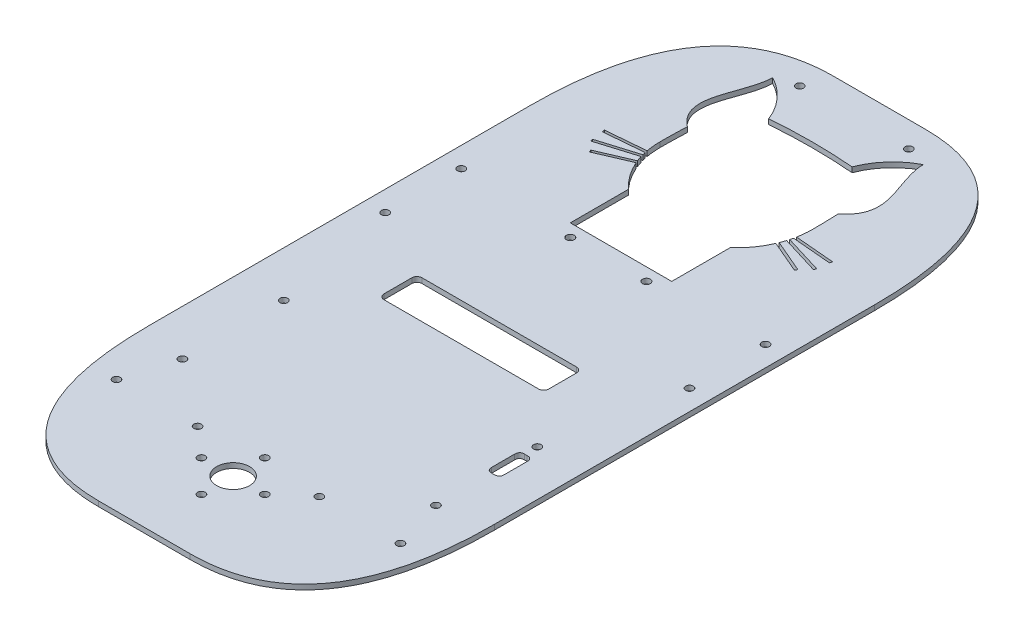
SolidWorks part; units mm, degrees
ref_plane "Спереди" through (0, 0, 0) normal (0, 0, 1) x (1, 0, 0)
ref_plane "Сверху" through (0, 0, 0) normal (0, 1, 0) x (1, 0, 0)
ref_plane "Справа" through (0, 0, 0) normal (1, 0, 0) x (0, 0, -1)
sketch "Эскиз1" plane through (0, 0, 0) normal (0, 1, 0) x (1, 0, 0)
  line L0 (0, 160) -> (0, -130) construction
  line L1 (-68, 160) -> (68, 160)
  line L2 (-68, 160) -> (-68, -130)
  line L3 (-68, -130) -> (68, -130)
  line L4 (68, 160) -> (68, -130)
  line L5 (-68, 0) -> (68, 0) construction
  dimension "D1" = 136
  dimension "D2" = 160
  dimension "D3" = 130
extrude "тело" add sketch "Эскиз1" along normal blind 2
sketch "Эскиз12" plane through (0, 2, 0) normal (0, 1, 0) x (1, 0, 0)
  line L0 (0, 160) -> (0, -130) construction
  line L1 (68, 160) -> (-68, 160) construction
  line L2 (-68, -130) -> (68, -130) construction
  line L3 (60, 55) -> (60, 25) construction
  line L4 (60, 40) -> (-60, 40) construction
  line L5 (-60, 55) -> (-60, 25) construction
  circle A0 centre (60, 55) radius 1.5
  circle A1 centre (-60, 55) radius 1.5
  circle A2 centre (-60, 25) radius 1.5
  circle A3 centre (60, 25) radius 1.5
  point P12 (-60, 40)
  point P17 (0, 40)
  dimension "D2" = 3
  dimension "D1" = 30
  dimension "D3" = 60
  dimension "D4" = 40
extrude "крепление подвески" cut sketch "Эскиз12" against normal through all
sketch "Эскиз8" plane through (0, 2, 0) normal (0, 1, 0) x (1, 0, 0)
  line L0 (-20, -130) -> (20, -130) construction
  line L1 (0, -130) -> (0, 160) construction
  line L2 (-68, -130) -> (68, -130) construction
  line L3 (68, 160) -> (-68, 160) construction
  circle A0 centre (-20, -130) radius 1.5
  circle A1 centre (20, -130) radius 1.5
  point P10 (0, -130)
  dimension "D1" = 3
  dimension "D2" = 40
  dimension "D3" = 130
extrude "крепление камеры" [suppressed] cut sketch "Эскиз8" against normal through all and the other way through all
sketch "Эскиз13" plane through (0, 2, 0) normal (0, 1, 0) x (1, 0, 0)
  line L0 (0, 160) -> (0, -130) construction
  line L1 (68, 160) -> (-68, 160) construction
  line L2 (-68, -130) -> (68, -130) construction
  line L3 (-57, 125) -> (57, 125) construction
  line L4 (-68, 15) -> (68, 15) construction
  line L5 (-57, -10) -> (57, -10) construction
  line L6 (-68, 160) -> (-68, -130) construction
  line L7 (-57, -85) -> (57, -85) construction
  line L8 (68, -130) -> (68, 160) construction
  line L9 (-25, 125) -> (-57, 125) construction
  line L10 (25, 125) -> (57, 125) construction
  line L11 (-57, -10) -> (-25, -10) construction
  line L12 (25, -10) -> (57, -10) construction
  line L13 (-57, -85) -> (-25, -85) construction
  line L14 (25, -85) -> (57, -85) construction
  circle A0 centre (-57, 125) radius 1.5
  circle A1 centre (57, 125) radius 1.5
  circle A2 centre (57, -10) radius 1.5
  circle A3 centre (-57, -10) radius 1.5
  circle A4 centre (-57, -85) radius 1.5
  circle A5 centre (57, -85) radius 1.5
  circle A6 centre (-25, 125) radius 1.5
  circle A7 centre (25, 125) radius 1.5
  circle A8 centre (25, -10) radius 1.5
  circle A9 centre (-25, -10) radius 1.5
  circle A10 centre (-25, -85) radius 1.5
  circle A11 centre (25, -85) radius 1.5
  point P18 (0, 125)
  point P19 (0, -10)
  point P20 (0, -85)
  point P27 (0, 15)
  dimension "D1" = 3
  dimension "D2" = 110
  dimension "D3" = 25
  dimension "D4" = 100
  dimension "D5" = 114
  dimension "D6" = 32
  dimension "D7" = 32
  dimension "D8" = 32
  dimension "D9" = 32
  dimension "D10" = 32
  dimension "D11" = 32
extrude "крепления уголков" [suppressed] cut sketch "Эскиз13" against normal through all
sketch "Эскиз9" plane through (0, 2, 0) normal (0, 1, 0) x (1, 0, 0)
  line L1 (-68, -130) -> (68, -130) construction
  circle A0 centre (0, -95) radius 6.5
  circle A1 centre (0, -95) radius 12.5 construction
  circle A2 centre (0, -82.5) radius 1.5
  circle A3 centre (12.5, -95) radius 1.5
  circle A4 centre (-12.5, -95) radius 1.5
  circle A5 centre (0, -107.5) radius 1.5
  dimension "D2" = 13
  dimension "D3" = 25
  dimension "D4" = 3
  dimension "D1" = 35
extrude "ось вращения качалки" cut sketch "Эскиз9" against normal through all
sketch "Эскиз5" plane through (0, 2, 0) normal (0, 1, 0) x (1, 0, 0)
  line L0 (-50, -65) -> (50, -25) construction
  line L1 (-50, -25) -> (50, -25) construction
  line L2 (-50, -25) -> (-50, -65) construction
  line L3 (-50, -65) -> (50, -65) construction
  line L4 (50, -25) -> (50, -65) construction
  line L5 (-50, -25) -> (50, -65) construction
  line L6 (-68, -130) -> (68, -130) construction
  circle A0 centre (-50, -25) radius 1.5
  circle A1 centre (50, -25) radius 1.5
  circle A2 centre (50, -65) radius 1.5
  circle A3 centre (-50, -65) radius 1.5
  point P12 (0, -45)
  dimension "D1" = 3
  dimension "D2" = 100
  dimension "D3" = 40
  dimension "D4" = 65
extrude "крепление raspberry" cut sketch "Эскиз5" against normal through all
sketch "Эскиз11" plane through (0, 2, 0) normal (0, 1, 0) x (1, 0, 0)
  line L0 (-32.5, 2.5) -> (32.5, 2.5) construction
  line L1 (-32.5, 10) -> (32.5, 10)
  line L2 (-32.5, 10) -> (-32.5, -5)
  line L3 (-32.5, -5) -> (32.5, -5)
  line L4 (32.5, 10) -> (32.5, -5)
  circle A0 centre (50, -25) radius 1.5 construction
  point P11 (0, 10)
  dimension "D3" = 20
  dimension "D1" = 65
  dimension "D2" = 15
extrude "отверстие под провода на нижний этаж" cut sketch "Эскиз11" against normal through all
fillet "Скругление3" radius 2 4 edges at (-32.5, 1, 5) (32.5, 1, 5) (32.5, 1, -10) (-32.5, 1, -10)
sketch "Эскиз14" plane through (0, 2, 0) normal (0, 1, 0) x (1, 0, 0)
  line L0 (0, 160) -> (0, -130) construction
  line L1 (68, 160) -> (-68, 160) construction
  line L2 (-68, -130) -> (68, -130) construction
  line L3 (-47.5, -125) -> (47.5, -125) construction
  line L4 (47.5, -115) -> (47.5, -135) construction
  line L5 (-12.5, -95) -> (12.5, -95) construction
  line L6 (-47.5, -115) -> (-47.5, -135) construction
  circle A0 centre (-47.5, -115) radius 1.5
  circle A1 centre (-47.5, -135) radius 1.5
  circle A2 centre (47.5, -115) radius 1.5
  circle A3 centre (47.5, -135) radius 1.5
  point P8 (0, -125)
  point P14 (-47.5, -125)
  point P15 (47.5, -125)
  dimension "D1" = 3
  dimension "D2" = 20
  dimension "D3" = 30
  dimension "D4" = 95
extrude "крепление стопоров" [suppressed] cut sketch "Эскиз14" against normal through all
sketch "Эскиз15" plane through (0, 2, 0) normal (0, 1, 0) x (1, 0, 0)
  line L0 (-21.5, 150) -> (21.5, 150) construction
  line L1 (68, 160) -> (-68, 160) construction
  circle A0 centre (21.5, 150) radius 1.5
  circle A1 centre (-21.5, 150) radius 1.5
  point P6 (0, 150)
  dimension "D1" = 3
  dimension "D2" = 10
  dimension "D3" = 43
extrude "Крепление фронтальной камеры" cut sketch "Эскиз15" against normal up to next
sketch "Эскиз16" plane through (0, 2, 0) normal (0, 1, 0) x (1, 0, 0)
  line L0 (-56, -85) -> (-24, -85) construction
  line L1 (-68, -130) -> (68, -130) construction
  line L2 (-68, 160) -> (-68, -130) construction
  line L3 (0, -130) -> (0, 160) construction
  line L4 (68, 160) -> (-68, 160) construction
  circle A0 centre (-56, -85) radius 1.5
  circle A1 centre (-24, -85) radius 1.5
  circle A2 centre (24, -85) radius 1.5
  circle A3 centre (56, -85) radius 1.5
  dimension "D1" = 32
  dimension "D4" = 3
  dimension "D2" = 45
  dimension "D3" = 12
extrude "Крепление силовых уголков со стороны буллета" cut sketch "Эскиз16" against normal up to next
sketch "Эскиз17" plane through (0, 2, 0) normal (0, 1, 0) x (1, 0, 0)
  line L1 (48, -30) -> (53, -30)
  line L2 (48, -30) -> (48, -43)
  line L3 (48, -43) -> (53, -43)
  line L4 (53, -30) -> (53, -43)
  circle A0 centre (50, -25) radius 1.5 construction
  dimension "D4" = 3
  dimension "D1" = 5
  dimension "D2" = 13
  dimension "D3" = 5
extrude "Отверстие по дпитание сервоприводов и шилда" cut sketch "Эскиз17" against normal up to next
sketch "Эскиз18" plane through (0, 2, 0) normal (0, 1, 0) x (1, 0, 0)
  line L0 (0, 0) -> (0, 160) construction
  line L1 (68, 160) -> (-68, 160) construction
  line L2 (-20, 58) -> (20, 58)
  line L3 (20, 58) -> (20, 81)
  line L5 (-20, 81) -> (-20, 58)
  line L6 (10, 58) -> (10, 43)
  line L7 (10, 43) -> (-10, 43)
  line L8 (-10, 43) -> (-10, 58)
  line L9 (28.2843, 93.3607) -> (-28.2843, 93.3607)
  line L11 (-29.2696, 96.7813) -> (-44.8695, 95.4286)
  line L12 (15, 53) -> (-15, 53) construction
  line L13 (-28.6963, 94.613) -> (-43.9353, 89.9676)
  line L16 (-27.5654, 91.5223) -> (-40.4203, 86.0016)
  line L17 (-29.474, 97.7673) -> (-44.9559, 96.4249)
  line L18 (-28.972, 95.5744) -> (-44.2269, 90.9242)
  line L19 (-27.9447, 92.4477) -> (-40.8149, 86.9204)
  line L20 (-44.9559, 96.4249) -> (-44.8695, 95.4286)
  line L21 (-44.2269, 90.9242) -> (-43.9353, 89.9676)
  line L22 (-40.8149, 86.9204) -> (-40.4203, 86.0016)
  line L23 (-29.356, 97.7776) -> (-44.9559, 96.4249) construction
  line L24 (-28.6804, 94.6179) -> (-43.9353, 89.9676) construction
  line L25 (-27.5501, 91.5289) -> (-40.4203, 86.0016) construction
  line L26 (40.8149, 86.9204) -> (40.4203, 86.0016)
  line L27 (44.2269, 90.9242) -> (43.9353, 89.9676)
  line L28 (44.9559, 96.4249) -> (44.8695, 95.4286)
  line L29 (27.9447, 92.4477) -> (40.8149, 86.9204)
  line L30 (28.972, 95.5744) -> (44.2269, 90.9242)
  line L31 (29.474, 97.7673) -> (44.9559, 96.4249)
  line L32 (27.5654, 91.5223) -> (40.4203, 86.0016)
  line L33 (28.6963, 94.613) -> (43.9353, 89.9676)
  line L34 (29.2696, 96.7813) -> (44.8695, 95.4286)
  arc A0 (20, 81) -> (-20, 81) centre (0, 103.3607) ccw construction
  circle A1 centre (15, 53) radius 1.55
  circle A2 centre (-15, 53) radius 1.55
  circle A3 centre (-50, -25) radius 1.5 construction
  arc A4 (-30, 103.3607) -> (-28.2843, 131.3607) centre (199.3322, 103.3607) cw
  arc A5 (-28.2843, 131.3607) -> (28.2843, 131.3607) centre (0, -67.6393) cw
  arc A6 (28.2843, 131.3607) -> (30, 103.3607) centre (-199.3322, 103.3607) cw
  arc A7 (-20, 81) -> (-27.5654, 91.5223) centre (0, 103.3607) cw
  arc A8 (20, 81) -> (27.5654, 91.5223) centre (0, 103.3607) ccw
  arc A9 (29.474, 97.7673) -> (30, 103.3607) centre (0, 103.3607) ccw
  arc A10 (-29.7135, 147.5209) -> (-16.4423, 132.687) centre (-42.569, 122.6661) cw
  arc A11 (29.7135, 147.5209) -> (16.4423, 132.687) centre (42.569, 122.6661) ccw
  arc A12 (28.972, 95.5744) -> (29.2696, 96.7813) centre (0, 103.3607) ccw
  arc A13 (27.9447, 92.4477) -> (28.6963, 94.613) centre (0, 103.3607) ccw
  arc A14 (-27.9447, 92.4477) -> (-28.6963, 94.613) centre (0, 103.3607) cw
  arc A15 (-28.972, 95.5744) -> (-29.2696, 96.7813) centre (0, 103.3607) cw
  arc A16 (-29.474, 97.7673) -> (-30, 103.3607) centre (0, 103.3607) cw
  spline S0 degree 3 poles (-29.7571, 113.9123) (-42.1018, 123.5014) (-29.7562, 136.265) (-29.7135, 147.5209) knots 0 0 0 0 1 1 1 1
  spline S1 degree 3 poles (29.7571, 113.9123) (42.1018, 123.5014) (29.7562, 136.265) (29.7135, 147.5209) knots 0 0 0 0 1 1 1 1
  point P9 (0, 43)
  point P15 (0, 58)
  point P25 (0, 53)
  dimension "D6" = 60
  dimension "D8" = 3.1
  dimension "D1" = 40
  dimension "D2" = 20
  dimension "D3" = 15
  dimension "D4" = 23
  dimension "D5" = 10
  dimension "D7" = 68
  dimension "D9" = 5
  dimension "D10" = 30
  dimension "D11" = 38
  dimension "D12" = 56.5685
  dimension "D13" = 1
  dimension "D14" = 1
  dimension "D15" = 1
fillet "Скругление4" radius 50 2 edges at (68, 1, 130) (-68, 1, -160) second distance 70 conic rho 0.5 first distance on face at (0, 1, 130) first distance on face at (0, 1, -160)
fillet "Скругление5" radius 70 2 edges at (-68, 1, 130) (68, 1, -160) second distance 50 conic rho 0.5 first distance on face at (-68, 1.25, -35) first distance on face at (68, 1.25, 5)
fillet "Скругление6" radius 2 4 edges at (48, 1, 43) (53, 1, 43) (48, 1, 30) (53, 1, 30) conic rho 0.5
sketch "Эскиз19" plane through (0, 2, 0) normal (0, 1, 0) x (1, 0, 0)
  line L1 (-95.3857, 162.9355) -> (76.7354, 162.9355)
  line L2 (-95.3857, 162.9355) -> (-95.3857, 60)
  line L3 (-95.3857, 60) -> (76.7354, 60)
  line L4 (76.7354, 162.9355) -> (76.7354, 60)
  circle A0 centre (-60, 55) radius 1.5 construction
  dimension "D1" = 5
extrude "Вырез-Вытянуть3" [suppressed] cut sketch "Эскиз19" against normal up to next
fillet "Скругление8" [suppressed] radius 10
extrude "Вырез-Вытянуть4" cut sketch "Эскиз18" against normal up to next contours S0 A4 A5 A10 | A6 S1 A11 A5 | A16 L17 L20 L11 A15 L18 L21 L13 A14 L9 A13 L33 L27 L30 A12 L34 L28 L31 A9 A6 A5 A4 | A14 L19 L22 L16 A7 L5 L2 L3 A8 L32 L26 L29 A13 L9 | A1 | A2 region at (0, 2, -76.9456) region at (0, 2, -112.4371) region at (-27.968, 2, -132.7806) region at (27.968, 2, -132.7806) region at (15, 2, -53) region at (-15, 2, -53)
